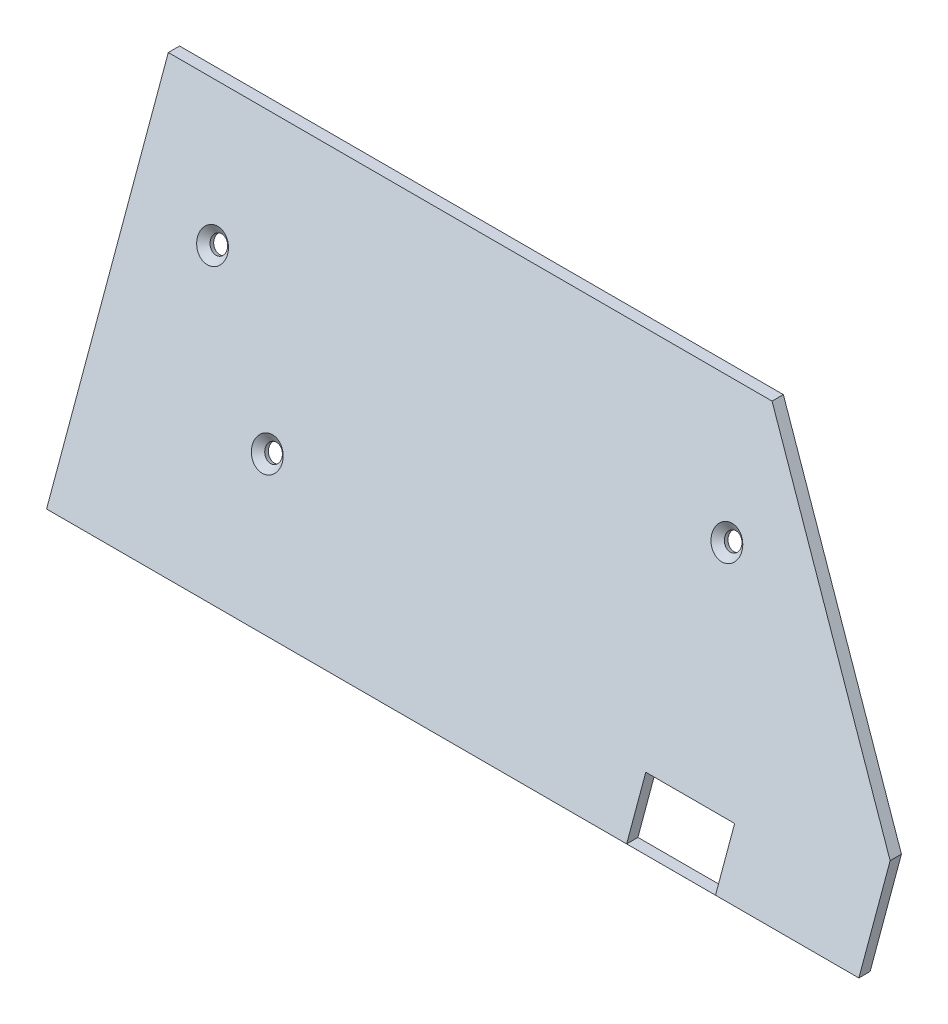
SolidWorks part; units mm, degrees
ref_plane "Front Plane" through (0, 0, 0) normal (0, 0, 1) x (1, 0, 0)
ref_plane "Top Plane" through (0, 0, 0) normal (0, 1, 0) x (1, 0, 0)
ref_plane "Right Plane" through (0, 0, 0) normal (1, 0, 0) x (0, 0, -1)
sketch "Sketch1" plane through (0, 0, 0) normal (1, 0, 0) x (0, 0, -1)
  line L0 (0, 0) -> (-2.3622, 0)
  line L1 (-2.3622, 0) -> (23.1157, 70)
  line L2 (23.1157, 70) -> (25.4779, 70)
  line L3 (25.4779, 70) -> (0, 0)
  dimension "D1" = 2.3622
  dimension "D2" = 2.3622
  dimension "D3" = 70
  dimension "D4" = 70
extrude "Main" add sketch "Sketch1" along normal mid plane 170
hole_wizard "BackBracketHoles" positions "Sketch2" profile "Sketch3" countersink size "M3" standard "ANSI Metric"
sketch "Sketch2" plane through (0, 0.7592, 2.0859) normal (0, 0.342, 0.9397) x (1, 0, 0)
  line L0 (-85, 73.6845) -> (-85, -0.8079) construction
  line L1 (85, -0.8079) -> (-85, -0.8079) construction
  point P0 (-67.6378, 50.0021)
  point P2 (-47.6378, 25.0021)
  dimension "D1" = 17.3622
  dimension "D2" = 50.81
  dimension "D3" = 25.81
  dimension "D4" = 37.3622
sketch "Sketch3" plane through (-67.6378, 47.7458, -15.0158) normal (1, 0, 0) x (0, -0.9397, 0.342)
  line L0 (0, 0) -> (0, 5)
  line L1 (0, 5) -> (1.75, 5)
  line L2 (1.75, 5) -> (1.75, 1.4)
  line L3 (1.75, 1.4) -> (3.15, 0)
  line L5 (3.15, 0) -> (0, 0)
  line L6 (-1.75, 1.4) -> (-3.15, 0) construction
  line L10 (0, 5) -> (-1.75, 5) construction
  line L11 (0, -6.35) -> (0, 107.95) construction
  dimension "Hole Dia." = 3.5
  dimension "Hole Depth" = 5
  dimension "Near C'Sink Dia." = 6.3
  dimension "Near C'Sink Angle" = 90
  dimension "Drill Angle" = 180
sketch "Sketch4" plane through (0, 0, 0) normal (0, 0, 1) x (1, 0, 0)
  line L0 (85.1927, 0.1116) -> (100, 0.1116)
  line L1 (100, 0.1116) -> (41.3567, 70)
  line L2 (85, 70) -> (-85, 70) construction
  line L3 (41.3567, 70) -> (41.3567, 0)
  line L4 (85, 0) -> (-85, 0) construction
  line L5 (41.3567, 0) -> (85.1927, 0.1116)
  line L6 (100, 0.1116) -> (100, 70)
  line L7 (100, 70) -> (41.3567, 70)
  line L8 (85, 70) -> (85, 0) construction
  dimension "D1" = 50
  dimension "D2" = 15
extrude "Cut-Extrude1" cut sketch "Sketch4" against normal blind 28.6 contours L6 L7 L1 region at (80.4522, 46.7039, 0)
hole_wizard "CSK for M3 Flat Head Machine Screw1" positions "Sketch5" profile "Sketch6" countersink size "M3" standard "ANSI Metric"
sketch "Sketch5" plane through (0, 0.7592, 2.0859) normal (0, 0.342, 0.9397) x (1, 0, 0)
  line L0 (30, 60.0021) -> (52.6886, 60.0021) construction
  line L1 (30, 60.0021) -> (30, 32.9616) construction
  point P0 (40, 50.0021)
  dimension "D1" = 10
  dimension "D2" = 10
sketch "Sketch6" plane through (40, 47.7458, -15.0158) normal (1, 0, 0) x (0, -0.9397, 0.342)
  line L0 (0, 0) -> (0, 5)
  line L1 (0, 5) -> (1.75, 5)
  line L2 (1.75, 5) -> (1.75, 1.4)
  line L3 (1.75, 1.4) -> (3.15, 0)
  line L5 (3.15, 0) -> (0, 0)
  line L6 (-1.75, 1.4) -> (-3.15, 0) construction
  line L10 (0, 5) -> (-1.75, 5) construction
  line L11 (0, -6.35) -> (0, 107.95) construction
  dimension "Hole Dia." = 3.5
  dimension "Hole Depth" = 5
  dimension "Near C'Sink Dia." = 6.3
  dimension "Near C'Sink Angle" = 90
  dimension "Drill Angle" = 180
sketch "Sketch7" plane through (0, 0, 0) normal (0, 0, 1) x (1, 0, 0)
  line L0 (36.4, 11.002) -> (36.4, 0.002) construction
  line L1 (36.4, 11.002) -> (55, 11.002)
  line L2 (36.4, 11.002) -> (36.4, 0.002)
  line L3 (36.4, 0.002) -> (55, 0.002)
  line L4 (55, 11.002) -> (55, 0.002)
  line L6 (36.4, 11.002) -> (55, 11.002) construction
  point P6 (0, 0)
extrude "Cut-Extrude3" cut sketch "Sketch7" against normal up to surface (34.0044 mm away) from offset 30 up to face at (40, 45.3421, -16.5032)
